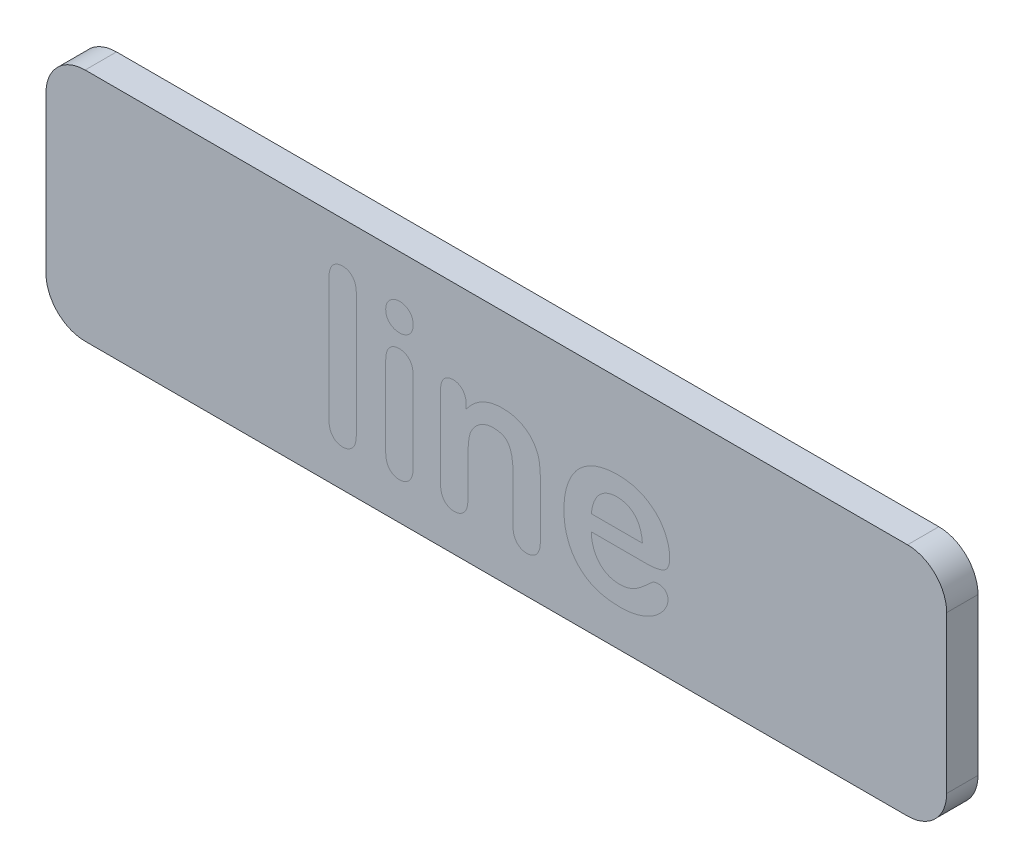
SolidWorks part; units mm, degrees
ref_plane "Front Plane" through (0, 0, 0) normal (1, 0, 0) x (0, 1, 0)
ref_plane "Top Plane" through (0, 0, 0) normal (0, 0, 1) x (0, 1, 0)
ref_plane "Right Plane" through (0, 0, 0) normal (0, 1, 0) x (-1, 0, 0)
sketch "Sketch1" plane through (0, 0, 0) normal (0, 0, 1) x (0, 1, 0)
  line L1 (-3, -11.5) -> (3, -11.5)
  line L2 (-3, -11.5) -> (-3, 11.5)
  line L3 (-3, 11.5) -> (3, 11.5)
  line L4 (3, -11.5) -> (3, 11.5)
  line L5 (-3, -11.5) -> (3, 11.5) construction
  line L6 (-3, 11.5) -> (3, -11.5) construction
  point P0 (0, 0)
  dimension "D1" = 6
  dimension "D2" = 23
extrude "Boss-Extrude1" add sketch "Sketch1" along normal blind 0.8
sketch "Sketch3" plane through (0, 0, 0.8) normal (0, 0, 1) x (1, 0, 0)
  line L0 (-11.5, -2) -> (11.5, -2) construction
  line L1 (-11.5, 3) -> (-11.5, -3) construction
  line L2 (11.5, -3) -> (11.5, 3) construction
  line L3 (-11.5, -3) -> (11.5, -3) construction
  text T0 "line" font "Arial Rounded MT Bold" height 4
  dimension "D1" = 1
extrude "Dimension-Cut" cut sketch "Sketch3" against normal blind 0.4
extrude "Dimension-Ext" add sketch "Sketch3<2>" against normal blind 0.4 separate body
sketch "Sketch3<2>" plane through (0, 0, 0.8) normal (0, 0, 1) x (1, 0, 0) same geometry as "Sketch3"
fillet "Fillet1" radius 1 4 edges at (11.5, -3, 0.4) (-11.5, -3, 0.4) (-11.5, 3, 0.4) (11.5, 3, 0.4)
